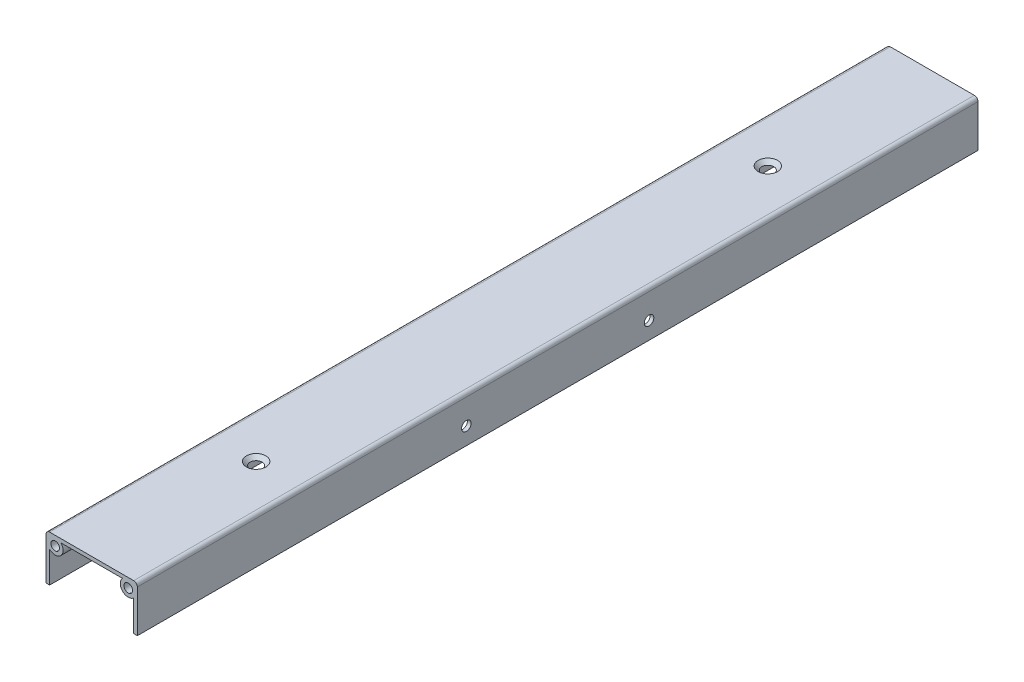
SolidWorks part; units mm, degrees
ref_plane "Front Plane" through (0, 0, 0) normal (0, 0, 1) x (1, 0, 0)
ref_plane "Top Plane" through (0, 0, 0) normal (0, 1, 0) x (1, 0, 0)
ref_plane "Right Plane" through (0, 0, 0) normal (1, 0, 0) x (0, 0, -1)
sketch "Sketch1" plane through (0, 0, 0) normal (0, 0, 1) x (1, 0, 0)
  line L0 (0, 31.75) -> (0, -31.75) construction
  line L1 (-31.75, -31.75) -> (31.75, -31.75)
  line L2 (-31.75, -31.75) -> (-31.75, 31.75)
  line L3 (-31.75, 31.75) -> (31.75, 31.75)
  line L4 (31.75, -31.75) -> (31.75, 31.75)
  line L5 (-31.75, -31.75) -> (31.75, 31.75) construction
  line L6 (-31.75, 31.75) -> (31.75, -31.75) construction
  line L7 (-31.75, 0) -> (31.75, 0) construction
  circle A0 centre (-25.4, 25.4) radius 3
  circle A1 centre (25.4, -25.4) radius 3
  circle A2 centre (-25.4, -25.4) radius 3
  circle A3 centre (25.4, 25.4) radius 3
  point P0 (0, 0)
  dimension "D3" = 6
  dimension "D9" = 50.8
  dimension "D4" = 50.8
  dimension "D1" = 63.5
  dimension "D2" = 63.5
  dimension "D5" = 6.35
extrude "Boss-Extrude1" add sketch "Sketch1" along normal mid plane 584.2
fillet "Fillet1" radius 2.54 4 edges at (-31.75, -31.75, 0) (31.75, -31.75, 0) (-31.75, 31.75, 0) (31.75, 31.75, 0)
shell "Shell1" thickness 2.54 removed face at (-28.4, -25.4, -292.1) removed face at (0, 0, 292.1)
sketch "Sketch3" plane through (0, 0, 292.1) normal (0, 0, 1) x (1, 0, 0)
  line L1 (-31.75, 29.21) -> (-31.75, -29.21) construction
  line L2 (-31.75, -0.1289) -> (31.9153, -0.1289)
  line L3 (-31.75, -0.1289) -> (-31.75, -31.8789)
  line L4 (-31.75, -31.8789) -> (31.9153, -31.8789)
  line L5 (31.9153, -0.1289) -> (31.9153, -31.8789)
  dimension "D1" = 31.75
extrude "Cut-Extrude2" cut sketch "Sketch3" against normal through all
hole_wizard "CSK for M6 Hex Socket Countersunk Head Screw1" positions "Sketch9" profile "Sketch8" countersink size "M6" standard "Lanco STD" end condition through all
sketch "Sketch9" plane through (0, 31.75, 0) normal (0, 1, 0) x (1, 0, 0)
  line L0 (29.21, -292.1) -> (-29.21, -292.1) construction
  line L1 (21.3781, 292.1) -> (-21.3781, 292.1) construction
  point P0 (0, 177.8)
  point P2 (0, -177.8)
  point P7 (0, 292.1)
  dimension "D1" = 114.3
  dimension "D2" = 114.3
sketch "Sketch8" plane through (0, 31.75, -177.8) normal (1, 0, 0) x (0, 0, 1)
  line L0 (0, 0) -> (0, 31.8789)
  line L1 (0, 31.8789) -> (3.2, 31.8789)
  line L2 (3.2, 31.8789) -> (3.2, 3.55)
  line L3 (3.2, 3.55) -> (6.75, 0)
  line L5 (6.75, 0) -> (0, 0)
  line L6 (-3.2, 3.55) -> (-6.75, 0) construction
  line L11 (0, -6.35) -> (0, 107.95) construction
  dimension "Thru Hole Dia." = 6.4
  dimension "Thru Hole Depth" = 31.8789
  dimension "Near C'Sink Dia." = 13.5
  dimension "Near C'Sink Angle" = 90
hole_wizard "M6 Clearance Hole1" positions "Sketch12" profile "Sketch11" hole size "M6" standard "ANSI Metric" end condition up to next
sketch "Sketch12" plane through (31.75, 0, 0) normal (1, 0, 0) x (0, 0, -1)
  line L0 (0, -50.1774) -> (0, 74.3545) construction
  line L2 (-292.1, -0.1289) -> (292.1, -0.1289) construction
  point P0 (63.5, 11.8118)
  point P2 (-63.5, 11.8118)
  dimension "D1" = 63.5
  dimension "D2" = 63.5
  dimension "D3" = 11.9407
sketch "Sketch11" plane through (31.75, 11.8118, -63.5) normal (0, 1, 0) x (0, 0, -1)
  line L0 (0, 0) -> (0, 2.54)
  line L1 (0, 2.54) -> (3.3, 2.54)
  line L2 (3.3, 2.54) -> (3.3, 0)
  line L5 (3.3, 0) -> (0, 0)
  line L11 (0, -6.35) -> (0, 107.95) construction
  dimension "Thru Hole Dia." = 6.6
  dimension "Thru Hole Depth" = 2.54
equation "\"D1@Boss-Extrude1\" = \"robot_width@Chassis.SLDASM\" - 6in"
